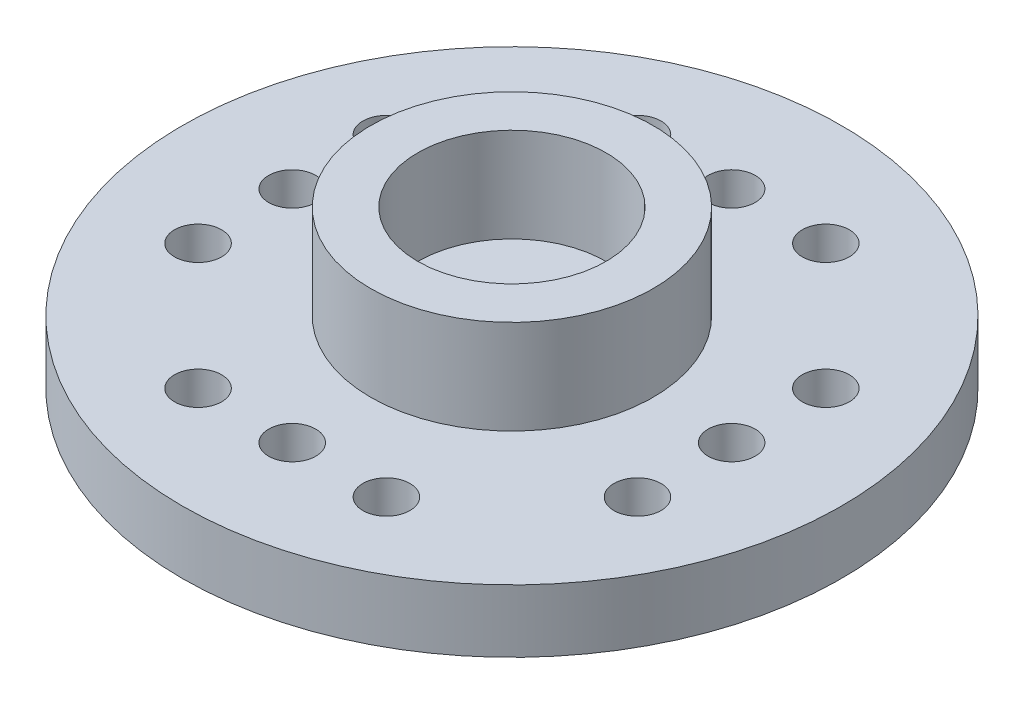
SolidWorks part; units mm, degrees
ref_plane "Front Plane" through (0, 0, 0) normal (0, 0, 1) x (1, 0, 0)
ref_plane "Top Plane" through (0, 0, 0) normal (0, 1, 0) x (1, 0, 0)
ref_plane "Right Plane" through (0, 0, 0) normal (1, 0, 0) x (0, 0, -1)
sketch "Sketch1" plane through (0, 0, 0) normal (0, 1, 0) x (1, 0, 0)
  circle A0 centre (0, 0) radius 10.5
  dimension "D1" = 21
extrude "Boss-Extrude1" add sketch "Sketch1" along normal blind 2
sketch "Sketch2" plane through (0, 2, 0) normal (0, 1, 0) x (1, 0, 0)
  circle A0 centre (0, 0) radius 4.5
  circle A1 centre (0, 0) radius 3
  dimension "D1" = 9
  dimension "D2" = 6
extrude "Boss-Extrude2" add sketch "Sketch2" along normal blind 3
sketch "Sketch3" plane through (0, 2, 0) normal (0, 1, 0) x (1, 0, 0)
  circle A0 centre (0, 0) radius 1
  dimension "D1" = 2
extrude "Cut-Extrude1" cut sketch "Sketch3" against normal blind 3
sketch "Sketch4" plane through (0, 0, 0) normal (0, -1, 0) x (1, 0, 0)
  circle A0 centre (0, 0) radius 4.25
  circle A1 centre (0, 0) radius 3.25
  circle A2 centre (0, 0) radius 2.75
  circle A3 centre (0, 0) radius 1 construction
  circle A4 centre (0, 0) radius 1
  circle M2 centre (0, 0) radius 1
  dimension "D1" = 8.5
  dimension "D2" = 6.5
  dimension "D3" = 5.5
extrude "Cut-Extrude2" cut sketch "Sketch4" against normal blind 0.5 contours A0 A1 | A2 M2 region at (-4.1298, 0, 0) region at (-2.6722, 0, 0)
sketch "Sketch5" plane through (0, 0, 0) normal (0, -1, 0) x (1, 0, 0)
  line L0 (-5.3137, 7) -> (6.4564, 7) construction
  line L1 (7, 4.9566) -> (7, -5.128) construction
  circle A0 centre (0, 7) radius 0.75
  circle A1 centre (3, 7) radius 0.75
  circle A2 centre (-3, 7) radius 0.75
  dimension "D3" = 1.5
  dimension "D4" = 1.5
  dimension "D5" = 1.5
  dimension "D1" = 7
  dimension "D2" = 7
  dimension "D6" = 3
  dimension "D7" = 3
extrude "Cut-Extrude3" cut sketch "Sketch5" against normal blind 2.5
mirror "Mirror1" about plane through (0, 0, 0) normal (0, 0, 1) of "Cut-Extrude3"
sketch "Sketch7" plane through (0, 0, 0) normal (0, -1, 0) x (1, 0, 0)
  line L0 (7, 4.7852) -> (7, -3.6424) construction
  circle A0 centre (7, 0) radius 0.75
  circle A1 centre (7, 3) radius 0.75
  circle A2 centre (7, -3) radius 0.75
  dimension "D2" = 1.5
  dimension "D3" = 1.5
  dimension "D4" = 1.5
  dimension "D1" = 7
  dimension "D5" = 3
  dimension "D6" = 3
extrude "Cut-Extrude4" cut sketch "Sketch7" against normal blind 2.5
mirror "Mirror2" about plane through (0, 0, 0) normal (1, 0, 0) of "Cut-Extrude4"
